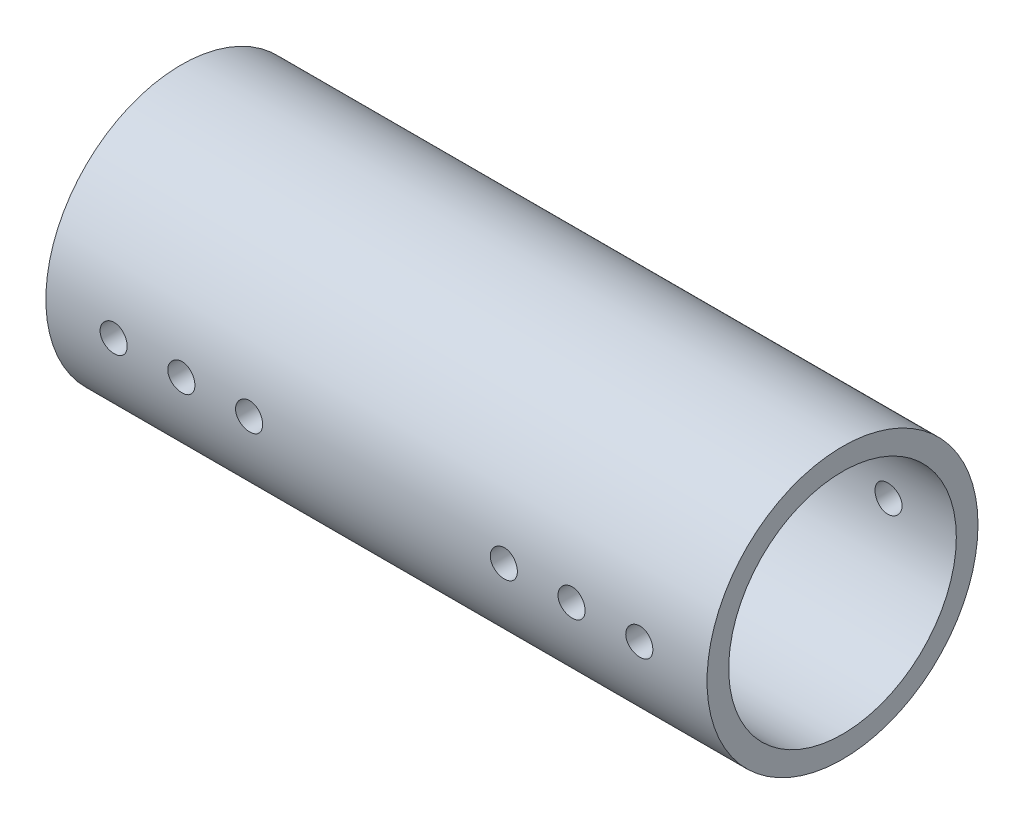
SolidWorks part; units mm, degrees
material "Zoltek Panex 33"
ref_plane "Спереди" through (0, 0, 0) normal (0, 0, 1) x (1, 0, 0)
ref_plane "Сверху" through (0, 0, 0) normal (0, 1, 0) x (1, 0, 0)
ref_plane "Справа" through (0, 0, 0) normal (1, 0, 0) x (0, 0, -1)
other "Configuration Table"
sketch "Эскиз2" plane through (0, 0, 0) normal (1, 0, 0) x (0, 0, -1)
  circle A0 centre (0, 0) radius 25
  circle A1 centre (0, 0) radius 21
  dimension "D1" = 50
  dimension "D2" = 42
extrude "Бобышка-Вытянуть2" add sketch "Эскиз2" along normal blind 122
ref_plane "Плоскость1" through (0, 0, 25) normal (0, 0, 1) x (1, 0, 0)
sketch "Эскиз4" plane through (0, 0, 25) normal (0, 0, 1) x (1, 0, 0)
  line L0 (0, -25) -> (122, -25) construction
  line L1 (122, -25) -> (122, 25) construction
  circle A0 centre (12.5, 0) radius 2.5
  circle A1 centre (109.5, 0) radius 2.5
  circle A2 centre (25, 0) radius 2.5
  circle A3 centre (37.5, 0) radius 2.5
  circle A4 centre (97, 0) radius 2.5
  circle A5 centre (84.5, 0) radius 2.5
  dimension "D1" = 5
  dimension "D4" = 5
  dimension "D6" = 5
  dimension "D8" = 5
  dimension "D10" = 5
  dimension "D11" = 5
  dimension "D2" = 12.5
  dimension "D3" = 25
  dimension "D5" = 12.5
  dimension "D7" = 12.5
  dimension "D9" = 12.5
  dimension "15" = 12.5
  dimension "D12" = 12.5
extrude "Вырез-Вытянуть2" cut sketch "Эскиз4" against normal through all and the other way blind 10 contours A0 | A1 | A2 | A3 | A5 | A4
equation "\"Diameter\"= 50мм"
equation "\"D1@Эскиз2\"= \"Diameter\""
equation "\"Length\"= 122мм"
equation "\"Thickness\"= 4мм"
equation "\"D1@Бобышка-Вытянуть2\"= \"Length\""
equation "\"D2@Эскиз2\" = \"Diameter\" - \"Thickness\" * 2"
equation "\"D4@Эскиз4\"=\"D1@Эскиз4\""
equation "\"D5@Эскиз4\"=\"D2@Эскиз4\""
equation "\"D3@Эскиз4\"=\"Diameter\"/2"
equation "\"D6@Эскиз4\"=\"D1@Эскиз4\""
equation "\"D8@Эскиз4\"=\"D6@Эскиз4\""
equation "\"D10@Эскиз4\"=\"D4@Эскиз4\""
equation "\"D11@Эскиз4\"=\"D4@Эскиз4\""
equation "\"D9@Эскиз4\"=\"D7@Эскиз4\""
